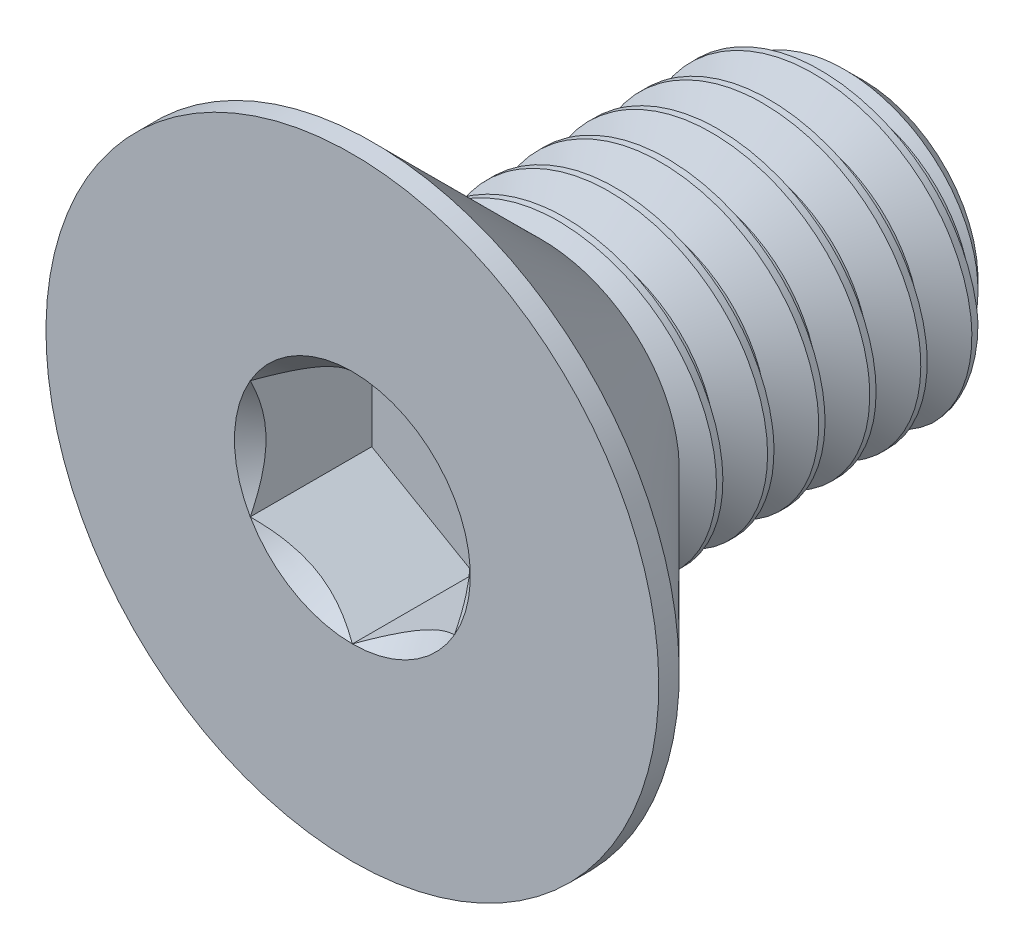
SolidWorks part; units mm, degrees
ref_plane "Front" through (0, 0, 0) normal (0, 0, 1) x (1, 0, 0)
ref_plane "Top" through (0, 0, 0) normal (0, 1, 0) x (1, 0, 0)
ref_plane "Right" through (0, 0, 0) normal (1, 0, 0) x (0, 0, -1)
sketch "Sketch1" plane through (0, 0, 0) normal (1, 0, 0) x (0, 0, -1)
  line L0 (0, 3) -> (0.2, 3) construction
  line L1 (0.2, 3) -> (1.7, 1.5) construction
  line L2 (0, 1.5) -> (5, 1.5)
  line L3 (5, 1.5) -> (5, 0)
  line L4 (5, 0) -> (0, 0)
  line L5 (0, 0) -> (0, 3) construction
  line L6 (0, 3) -> (0, -3) construction
  line L7 (5, 1.5) -> (5, -1.5) construction
  line L8 (0, -3) -> (0.2, -3) construction
  line L9 (0.2, -3) -> (1.7, -1.5) construction
  line L11 (0, 1.5) -> (0, 0)
  line L12 (1.7, 1.5) -> (1.7, 0) construction
revolve "Revolve1" add sketch "Sketch1" angle 360 mid plane about L4
sketch "Sketch3" plane through (0, 0, -5) normal (0, 0, -1) x (-1, 0, 0)
  circle A0 centre (0, 0) radius 1.5
curve "Helix/Spiral1" pitch 0.5 height 5 radius 1.5 centre (0, 0, -5) axis (0, 0, 1) start towards (0, 1, 0)
sketch "Sketch2" plane through (0, 0, 0) normal (1, 0, 0) x (0, 0, -1)
  line L0 (5, 1.5) -> (5.4375, 1.5)
  line L1 (5.4375, 1.5) -> (5.25, 1.1752)
  line L2 (5.25, 1.1752) -> (5.1875, 1.1752)
  line L3 (5.1875, 1.1752) -> (5, 1.5)
  line L4 (5.0938, 1.3376) -> (5.3437, 1.3376) construction
  dimension "D1" = 60
  dimension "D2" = 0.0625
  dimension "D3" = 0.25
chamfer "Chamfer1" distance 0.375 angle 45 1 edges at (0, 1.5, -5)
sweep "Cut-Sweep1" cut profiles "Sketch2" path "Helix/Spiral1" align with end faces yes
sketch "Sketch7" plane through (0, 0, 0) normal (1, 0, 0) x (0, 0, -1)
  line L0 (0, 3) -> (0.2, 3) construction
  line L1 (0.2, 3) -> (1.7, 1.5) construction
  line L2 (0, 3) -> (0.2, 3)
  line L3 (0.2, 3) -> (1.7, 1.5)
  line L4 (1.7, 1.5) -> (1.7, 0) construction
  line L5 (1.7, 1.5) -> (1.7, 0)
  line L7 (0, 0) -> (0, 3) construction
  line L8 (0, 0) -> (0, 3)
  line L9 (0, 0) -> (1.7, 0)
  line L10 (3.3, 0) -> (-3.3, 0) construction
revolve "Revolve2" add sketch "Sketch7" angle 360 mid plane about L9
ref_plane "Plane1" through (0, 0, -1.7) normal (0, 0, 1) x (1, 0, 0)
sketch "Sketch8" plane through (0, 0, -1.7) normal (0, 0, 1) x (1, 0, 0)
  circle A0 centre (0, 0) radius 1.5
extrude "Boss-Extrude1" add sketch "Sketch8" against normal through all draft 45
sketch "Sketch5" plane through (0, 0, 0) normal (0, 0, 1) x (1, 0, 0)
  line L1 (1, -0.5774) -> (1, 0.5774)
  line L2 (1, 0.5774) -> (0, 1.1547)
  line L3 (0, 1.1547) -> (-1, 0.5774)
  line L4 (-1, 0.5774) -> (-1, -0.5774)
  line L5 (-1, -0.5774) -> (0, -1.1547)
  line L6 (0, -1.1547) -> (1, -0.5774)
  circle A0 centre (0, 0) radius 1 construction
  dimension "Hex" = 2
extrude "Cut-Extrude2" cut sketch "Sketch5" against normal blind 1.19
sketch "Sketch6" plane through (0, 0, 0) normal (0, 0, 1) x (1, 0, 0)
  circle A0 centre (0, 0) radius 1.1547
extrude "Cut-Extrude3" cut sketch "Sketch6" against normal blind 1.19 draft 45
sketch "Sketch9" [suppressed] plane through (0, 0, -5.5) normal (0, 0, 1) x (1, 0, 0)
  circle A1 centre (0, 0) radius 5
  circle A2 centre (0, 0) radius 5
  point P0 (0, 5)
  dimension "D1" = 0
extrude "Boss-Extrude2" [suppressed] add sketch "Sketch9" against normal offset from surface (18.5 mm away) 26 up to face at (0, 1.125, -5)
fillet "Fillet1" [suppressed] radius 0.3
sketch "Sketch10" plane through (0, 0, 0) normal (1, 0, 0) x (0, 0, -1)
  line L0 (5, 1.5) -> (5, -1.5) construction
  point P0 (4.25, -1.5)
  dimension "D1" = 0.75
equation "\"D3@Helix/Spiral1\" = \"Lg@Sketch1\""
equation "\"D2@Sketch2\" = \"D4@Helix/Spiral1\" * .125"
equation "\"D3@Sketch2\" = \"D4@Helix/Spiral1\" * .5"
equation "\"D1@Chamfer1\" = \"D4@Helix/Spiral1\" * .75"
equation "\"D1@Cut-Extrude2\" = \"Head Ht@Sketch1\" * .7"
equation "\"D1@Sketch10\" = \"D4@Helix/Spiral1\" * 1.5"
equation "\"D1@Cut-Extrude3\" = \"D1@Cut-Extrude2\""
equation "\"D1@Fillet1\" = \"Dia@Sketch1\" * .1"
